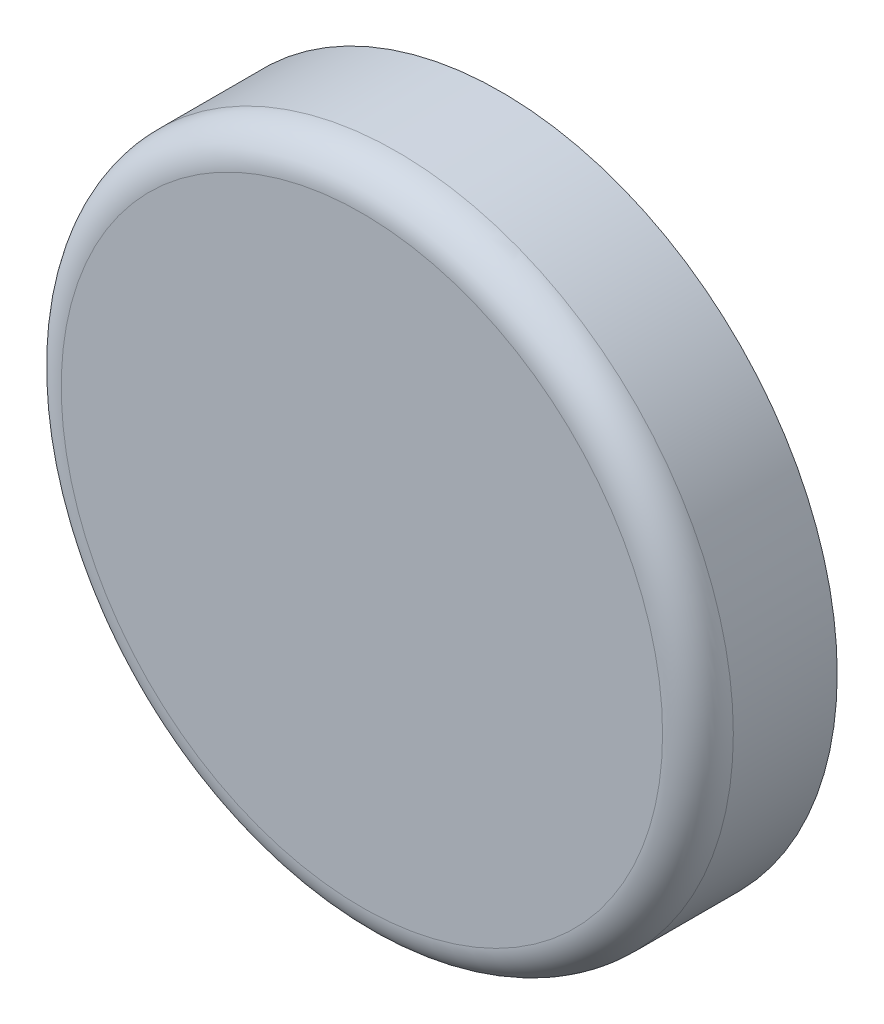
SolidWorks part; units mm, degrees
ref_plane "Front Plane" through (0, 0, 0) normal (0, 0, 1) x (1, 0, 0)
ref_plane "Top Plane" through (0, 0, 0) normal (0, 1, 0) x (1, 0, 0)
ref_plane "Right Plane" through (0, 0, 0) normal (1, 0, 0) x (0, 0, -1)
sketch "Sketch1" plane through (0, 0, 0) normal (0, 0, 1) x (1, 0, 0)
  circle A0 centre (0, 0) radius 12.065
  dimension "D1" = 24.13
extrude "Boss-Extrude1" add sketch "Sketch1" along normal blind 5
sketch "Sketch3" plane through (0, 0, 0) normal (0, 0, -1) x (-1, 0, 0)
  circle A0 centre (0, 0) radius 1.5
  dimension "D1" = 3
extrude "Boss-Extrude2" add sketch "Sketch3" along normal blind 2.54
fillet "Fillet1" radius 1.27 1 edges at (12.065, 0, 5)
